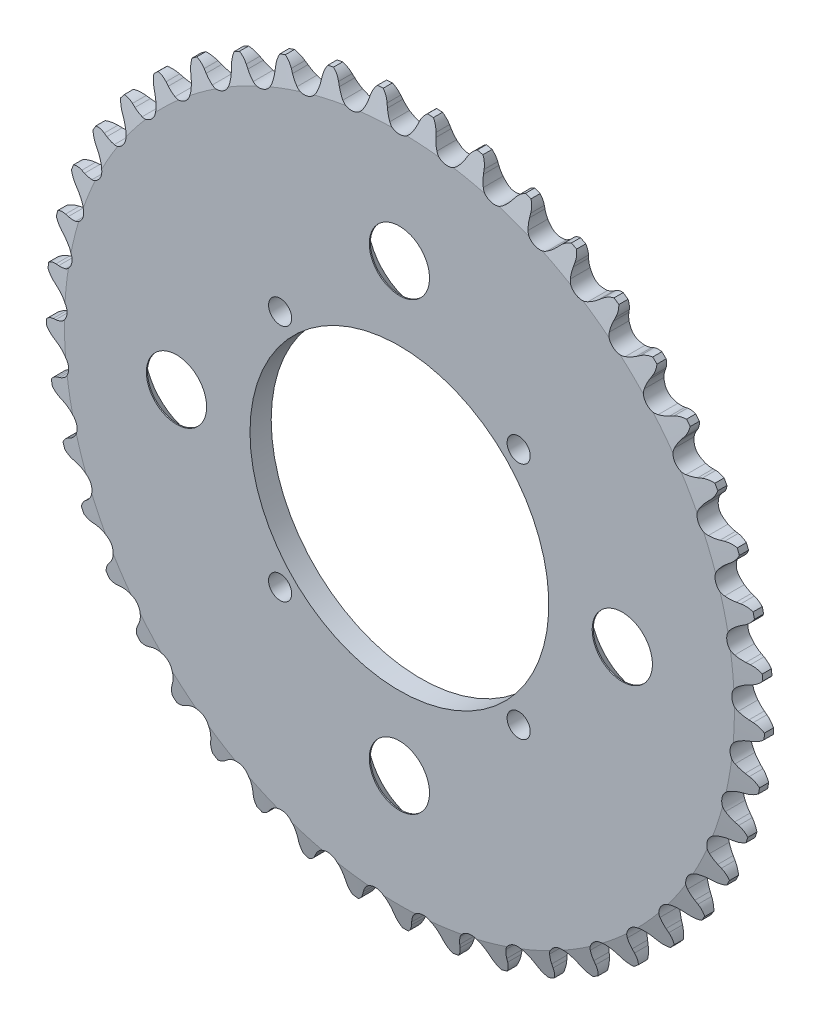
SolidWorks part; units mm, degrees
ref_plane "Front Plane" through (0, 0, 0) normal (0, 0, 1) x (1, 0, 0)
ref_plane "Top Plane" through (0, 0, 0) normal (0, 1, 0) x (1, 0, 0)
ref_plane "Right Plane" through (0, 0, 0) normal (1, 0, 0) x (0, 0, -1)
ref_axis "Axis1" through (0, 0, -88.99) along (0, 0, 1)
sketch "Sprocket-BaseSketch" plane through (0, 0, 0) normal (1, 0, 0) x (0, 0, -1)
  line L0 (1.397, 19.685) -> (1.397, 44.1346)
  line L1 (1.397, 44.1346) -> (0.6032, 47.3096)
  line L2 (0.6032, 47.3096) -> (-0.6032, 47.3096)
  line L3 (-0.6032, 47.3096) -> (-1.397, 44.1346)
  line L4 (-1.397, 44.1346) -> (-1.397, 19.685)
  line L5 (-1.397, 19.685) -> (1.397, 19.685)
  line L6 (5.588, 0) -> (-1.7463, 0) construction
  dimension "Hub Surface" = 1.397
  dimension "RightSide (1)" = 0.7938
  dimension "RightSide (2)" = 3.175
  dimension "OD" = 47.3096
  dimension "LeftSide (1)" = 0.7938
  dimension "LeftSide (2)" = 3.175
  dimension "Tooth Width" = 2.794
  dimension "Bore" = 19.685
revolve "25 (04C) ANSI (ISO) Chain Number, 3.584in P.D." add sketch "Sprocket-BaseSketch" angle 360 about L6
sketch "Tooth-Sketch" plane through (0, 0, 0) normal (0, 0, 1) x (1, 0, 0)
  line L0 (0, 0) -> (0, 60.6873) construction
  line L1 (1.9601, 45.6267) -> (2.1209, 46.0788)
  line L2 (-1.9601, 45.6267) -> (-2.1209, 46.0788)
  line L3 (0, 45.5155) -> (6.3345, 45.0725) construction
  line L4 (0, 45.5155) -> (-6.3345, 45.0725) construction
  arc A0 (-1.3674, 44.5098) -> (1.3674, 44.5098) centre (0, 45.5155) ccw
  arc A1 (1.3674, 44.5098) -> (1.9601, 45.6267) centre (-2.128, 47.0806) ccw
  arc A2 (-1.3674, 44.5098) -> (-1.9601, 45.6267) centre (2.128, 47.0806) cw
  arc A3 (2.1209, 46.0788) -> (4.6115, 47.8365) centre (4.6115, 45.193) cw
  arc A4 (-2.1209, 46.0788) -> (-4.6115, 47.8365) centre (-4.6115, 45.193) ccw
  arc A5 (4.6115, 47.8365) -> (-4.6115, 47.8365) centre (0, 0) ccw
extrude "Tooth-Cut, Number of teeth: 45" cut sketch "Tooth-Sketch" against normal through all and the other way through all
pattern_circular "Tooth Pattern, 45 / 45" count 45 every 8 about axis through (0, 0, -88.99) along (0, 0, 1) of "Tooth-Cut, Number of teeth: 45"
sketch "Sketch1" plane through (0, 0, -1.397) normal (0, 0, -1) x (-1, 0, 0)
  line L0 (0, 0) -> (15.7154, -15.7154) construction
  line L1 (0, 0) -> (13.3515, 0) construction
  circle A0 centre (29.3687, 0) radius 3.9687
  circle A1 centre (0, -29.3687) radius 3.9688
  circle A2 centre (-29.3687, 0) radius 3.9687
  circle A3 centre (0, 29.3688) radius 3.9688
  circle A4 centre (15.7154, -15.7154) radius 1.524
  circle A5 centre (-15.7154, -15.7154) radius 1.524
  circle A6 centre (-15.7154, 15.7154) radius 1.524
  circle A7 centre (15.7154, 15.7154) radius 1.524
  dimension "D1" = 7.9375
  dimension "D6" = 3.048
  dimension "D2" = 29.3687
  dimension "D4" = 45
  dimension "D5" = 22.225
  dimension "D3" = 4
  dimension "D7" = 4
extrude "Cut-Extrude1" cut sketch "Sketch1" against normal through all
chamfer "Chamfer1" distance 3.048 angle 41 4 edges at (-3.9687, -29.3687, -1.397) (-33.3375, 0, -1.397) (-3.9688, 29.3688, -1.397) (25.4, 0, -1.397) first distance on face at (-17.2394, 15.7154, -1.397)
